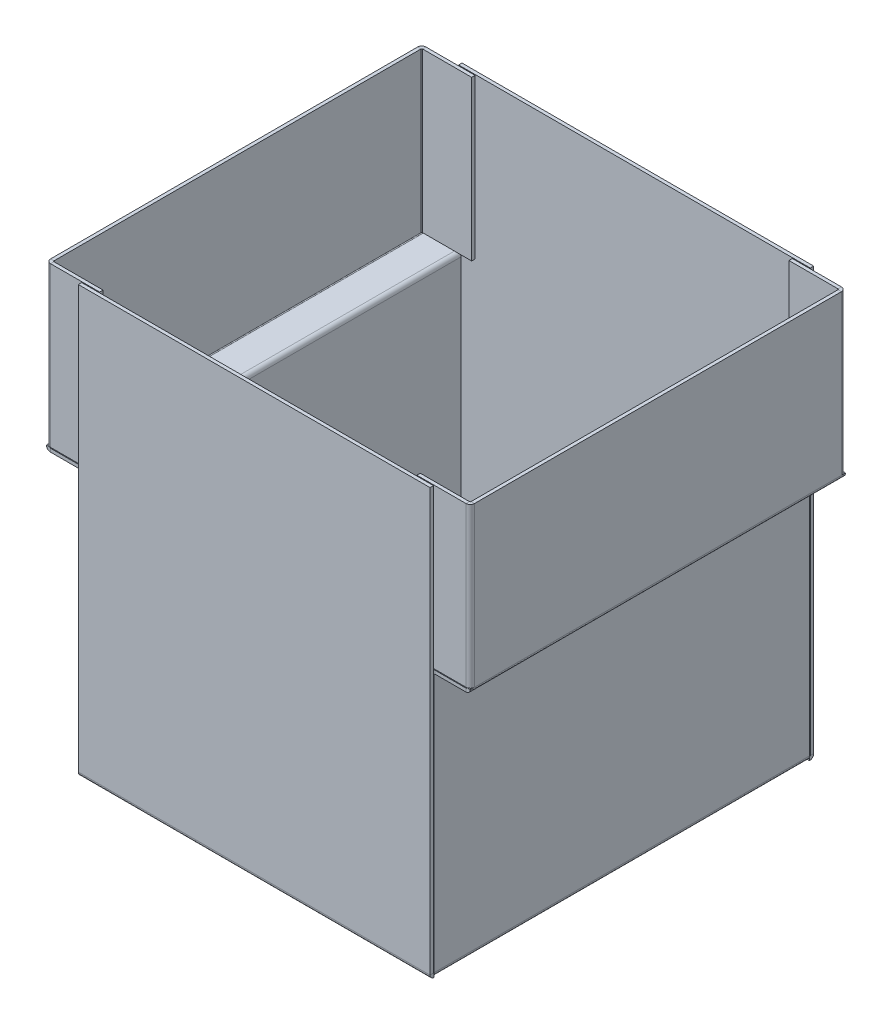
SolidWorks part; units mm, degrees
note: The reader was unsure of these and kept them because the rebuilt part matched: flange length of "Edge-Flange4", "Edge-Flange5", "Edge-Flange6", "Edge-Flange7", "Edge-Flange10", "Edge-Flange11", "Edge-Flange12", "Edge-Flange13", "Edge-Flange14".
material "6061 Alloy"
ref_plane "Front" through (0, 0, 0) normal (0, 0, 1) x (1, 0, 0)
ref_plane "Top" through (0, 0, 0) normal (0, 1, 0) x (1, 0, 0)
ref_plane "Right" through (0, 0, 0) normal (1, 0, 0) x (0, 0, -1)
sketch "Sketch6" plane through (0, 0, 0) normal (0, 1, 0) x (1, 0, 0)
  line L1 (-165, -180) -> (165, -180)
  line L2 (-165, -180) -> (-165, 180)
  line L3 (-165, 180) -> (165, 180)
  line L4 (165, -180) -> (165, 180)
  line L5 (-165, -180) -> (165, 180) construction
  line L6 (-165, 180) -> (165, -180) construction
  point P1 (0, 0)
  dimension "D1" = 360
  dimension "D2" = 330
base flange "Base-Flange2" sketch "Sketch6" thickness 3.175 reverse thickness direction no parameters "D1"=0.7366
edge flange "Edge-Flange4" sketch "Sketch34" flange angle 90 flange length 400 flange position material inside bend radius 0.7366 thickness 3.175 relief rectangular parameters "D6"=10
sketch "Sketch34" plane through (0, 0, 180) normal (0, 0, 1) x (1, 0, 0)
  line L0 (-165, 0) -> (165, 0) construction
  line L1 (-165, 0) -> (165, 0)
  line L2 (-165, 0) -> (-165, 396.825)
  line L3 (-165, 396.825) -> (165, 396.825)
  line L4 (165, 396.825) -> (165, 0)
bend "EdgeBend4" bend radius 0.7366 bend angle 90 parameters "D5"=1
edge flange "Edge-Flange5" sketch "Sketch37" flange angle 90 flange length 400 flange position material inside bend radius 0.7366 thickness 3.175 relief rectangular parameters "D6"=10
sketch "Sketch37" plane through (0, 0, -180) normal (0, 0, -1) x (-1, 0, 0)
  line L0 (-165, 0) -> (165, 0) construction
  line L1 (-165, 0) -> (165, 0)
  line L2 (-165, 0) -> (-165, 396.825)
  line L3 (-165, 396.825) -> (165, 396.825)
  line L4 (165, 396.825) -> (165, 0)
bend "EdgeBend5" bend radius 0.7366 bend angle 90 parameters "D5"=2
edge flange "Edge-Flange6" sketch "Sketch40" flange angle 90 flange length 250 flange position material inside bend radius 0.7366 thickness 3.175 relief none parameters "D6"=10
sketch "Sketch40" plane through (165, 0, 0) normal (1, 0, 0) x (0, 0, -1)
  line L0 (-176.0884, 0) -> (176.0884, 0) construction
  line L1 (-176.0884, 0) -> (176.0884, 0)
  line L2 (-176.0884, 0) -> (-176.0884, 246.825)
  line L3 (-176.0884, 246.825) -> (176.0884, 246.825)
  line L4 (176.0884, 246.825) -> (176.0884, 0)
bend "EdgeBend6" bend radius 0.7366 bend angle 90 parameters "D5"=3
edge flange "Edge-Flange7" sketch "Sketch43" flange angle 90 flange length 250 flange position material inside bend radius 0.7366 thickness 3.175 relief none parameters "D6"=10
sketch "Sketch43" plane through (-165, 0, 0) normal (-1, 0, 0) x (0, 0, 1)
  line L0 (-176.0884, 0) -> (176.0884, 0) construction
  line L1 (-176.0884, 0) -> (176.0884, 0)
  line L2 (-176.0884, 0) -> (-176.0884, 246.825)
  line L3 (-176.0884, 246.825) -> (176.0884, 246.825)
  line L4 (176.0884, 246.825) -> (176.0884, 0)
bend "EdgeBend7" bend radius 0.7366 bend angle 90 parameters "D5"=4
edge flange "Edge-Flange10" sketch "Sketch54" flange angle 90 flange length 37 flange position material inside bend radius 0.7366 thickness 3.175 relief rectangular parameters "D6"=10
sketch "Sketch54" plane through (-165, 246.825, 0) normal (0, 1, 0) x (0, 0, -1)
  line L0 (-176.0884, 0) -> (176.0884, 0) construction
  line L1 (-176.0884, 0) -> (176.0884, 0)
  line L2 (-176.0884, 0) -> (-176.0884, 33.825)
  line L3 (-176.0884, 33.825) -> (176.0884, 33.825)
  line L4 (176.0884, 33.825) -> (176.0884, 0)
bend "EdgeBend10" bend radius 0.7366 bend angle 90 parameters "D5"=5
edge flange "Edge-Flange11" sketch "Sketch57" flange angle 90 flange length 37 flange position material inside bend radius 0.7366 thickness 3.175 relief rectangular parameters "D6"=10
sketch "Sketch57" plane through (165, 246.825, 0) normal (0, 1, 0) x (0, 0, 1)
  line L0 (-176.0884, 0) -> (176.0884, 0) construction
  line L1 (-176.0884, 0) -> (176.0884, 0)
  line L2 (-176.0884, 0) -> (-176.0884, 33.825)
  line L3 (-176.0884, 33.825) -> (176.0884, 33.825)
  line L4 (176.0884, 33.825) -> (176.0884, 0)
bend "EdgeBend11" bend radius 0.7366 bend angle 90 parameters "D5"=6
edge flange "Edge-Flange12" sketch "Sketch60" flange angle 90 flange length 153.18 flange position material inside bend radius 0.7366 thickness 3.175 relief rectangular parameters "D6"=10
sketch "Sketch60" plane through (-198.825, 246.825, 0) normal (-1, 0, 0) x (0, 0, 1)
  line L2 (-176.0884, 0) -> (-176.0884, 150.005)
  line L3 (-176.0884, 150.005) -> (176.0884, 150.005)
  line L4 (176.0884, 150.005) -> (176.0884, 0)
  line L7 (-176.0884, 0) -> (176.0884, 0) construction
  line L8 (-176.0884, 0) -> (176.0884, 0)
bend "EdgeBend12" bend radius 0.7366 bend angle 90 parameters "D5"=7
edge flange "Edge-Flange13" sketch "Sketch63" flange angle 90 flange length 153.18 flange position material inside bend radius 0.7366 thickness 3.175 relief rectangular parameters "D6"=10
sketch "Sketch63" plane through (198.825, 246.825, 0) normal (1, 0, 0) x (0, 0, -1)
  line L0 (-176.0884, 0) -> (176.0884, 0) construction
  line L1 (-176.0884, 0) -> (176.0884, 0)
  line L2 (-176.0884, 0) -> (-176.0884, 150.005)
  line L3 (-176.0884, 150.005) -> (176.0884, 150.005)
  line L4 (176.0884, 150.005) -> (176.0884, 0)
bend "EdgeBend13" bend radius 0.7366 bend angle 90 parameters "D5"=8
edge flange "Edge-Flange14" sketch "Sketch68" flange profiles "Sketch68", "Sketch79", "Sketch81", "Sketch83" flange angle 90 flange length 50 bend radius 0.7366 thickness 3.175 relief none parameters "D6"=10, "D8"=1
sketch "Sketch68" plane through (-195.65, 0, 176.0884) normal (0, 0, 1) x (0, -1, 0)
  line L2 (-396.83, 0) -> (-396.83, 46.825)
  line L3 (-396.83, 46.825) -> (-247.5616, 46.825)
  line L4 (-247.5616, 46.825) -> (-247.5616, 0)
  line L15 (-247.5616, 0) -> (-396.83, 0) construction
  line L16 (-247.5616, 0) -> (-396.83, 0)
sketch "Sketch79" plane through (-195.65, 0, -176.0884) normal (0, 0, -1) x (0, 1, 0)
  line L0 (396.83, 0) -> (247.5616, 0) construction
  line L1 (396.83, 0) -> (247.5616, 0)
  line L2 (247.5616, 0) -> (247.5616, 46.825)
  line L3 (247.5616, 46.825) -> (396.83, 46.825)
  line L4 (396.83, 46.825) -> (396.83, 0)
sketch "Sketch81" plane through (195.65, 0, -176.0884) normal (0, 0, -1) x (0, -1, 0)
  line L0 (-247.5616, 0) -> (-396.83, 0) construction
  line L1 (-247.5616, 0) -> (-396.83, 0)
  line L2 (-396.83, 0) -> (-396.83, 46.825)
  line L3 (-396.83, 46.825) -> (-247.5616, 46.825)
  line L4 (-247.5616, 46.825) -> (-247.5616, 0)
sketch "Sketch83" plane through (195.65, 0, 176.0884) normal (0, 0, 1) x (0, 1, 0)
  line L0 (396.83, 0) -> (247.5616, 0) construction
  line L1 (396.83, 0) -> (247.5616, 0)
  line L2 (247.5616, 0) -> (247.5616, 46.825)
  line L3 (247.5616, 46.825) -> (396.83, 46.825)
  line L4 (396.83, 46.825) -> (396.83, 0)
bend "EdgeBend14" bend radius 0.7366 bend angle 90 parameters "D5"=9
bend "EdgeBend18" bend radius 0.7366 bend angle 90 parameters "D5"=11
bend "EdgeBend19" bend radius 0.7366 bend angle 90 parameters "D5"=12
bend "EdgeBend20" bend radius 0.7366 bend angle 90 parameters "D5"=13
sketch "Bend-Lines5" [suppressed] plane through (0, 0, 0) normal (0, 1, 0) x (1, 0, 0)
sketch "Bounding-Box5" [suppressed] plane through (0, 0, 0) normal (0, 1, 0) x (1, 0, 0)
sheet metal parameters "Sheet-Metal6" thickness 3.175 parameters "D1"=0.7366
flat pattern "Flat-Pattern6" [suppressed]
sketch "Bend-Lines6" plane through (0, 0, 0) normal (0, 1, 0) x (1, 0, 0)
sketch3d "Bounding-Box6" [suppressed]
  line L0 (-165.1, -177.8, 0) -> (-165.1, 177.8, 0) construction
  line L1 (165.1, -177.8, 0) -> (165.1, 177.8, 0) construction
  line L2 (-165.1, -177.8, 0) -> (165.1, -177.8, 0) construction
  line L3 (-165.1, 177.8, 0) -> (165.1, 177.8, 0) construction
sheet metal parameters "Sheet-Metal10" thickness 3.175 parameters "D1"=0.7366
flat pattern "Flat-Pattern6"
sketch "Bend-Lines6" plane through (0, 0, 0) normal (0, 1, 0) x (1, 0, 0)
  line L0 (-165.1, -175.7137) -> (165.1, -175.7137) construction
  line L1 (-165.1, -175.7137) -> (165.1, -175.7137) construction
sketch3d "Bounding-Box6" [suppressed]
  line L0 (-165.1, -478.4275, 0) -> (-165.1, 177.8, 0) construction
  line L1 (165.1, -478.4275, 0) -> (165.1, 177.8, 0) construction
  line L2 (-165.1, -478.4275, 0) -> (165.1, -478.4275, 0) construction
  line L3 (-165.1, 177.8, 0) -> (165.1, 177.8, 0) construction
bend of the flat pattern "Flatten-<EdgeBend4>1"
sheet metal parameters "Sheet-Metal11" thickness 3.175 parameters "D1"=0.7366
flat pattern "Flat-Pattern6"
sketch "Bend-Lines6" plane through (0, 0, 0) normal (0, 1, 0) x (1, 0, 0)
  line L0 (-165.1, -175.7137) -> (165.1, -175.7137) construction
  line L1 (-165.1, -175.7137) -> (165.1, -175.7137) construction
  line L2 (165.1, 175.7137) -> (-165.1, 175.7137) construction
  line L3 (165.1, 175.7137) -> (-165.1, 175.7137) construction
sketch3d "Bounding-Box6" [suppressed]
  line L0 (-165.1, -478.4275, 0) -> (-165.1, 478.4275, 0) construction
  line L1 (165.1, -478.4275, 0) -> (165.1, 478.4275, 0) construction
  line L2 (-165.1, -478.4275, 0) -> (165.1, -478.4275, 0) construction
  line L3 (-165.1, 478.4275, 0) -> (165.1, 478.4275, 0) construction
bend of the flat pattern "Flatten-<EdgeBend4>1"
bend of the flat pattern "Flatten-<EdgeBend5>1"
sheet metal parameters "Sheet-Metal12" thickness 3.175 parameters "D1"=0.7366
flat pattern "Flat-Pattern6"
sketch "Bend-Lines6" plane through (0, 0, 0) normal (0, 1, 0) x (1, 0, 0)
  line L0 (-165.1, -175.7137) -> (165.1, -175.7137) construction
  line L1 (-165.1, -175.7137) -> (165.1, -175.7137) construction
  line L2 (165.1, 175.7137) -> (-165.1, 175.7137) construction
  line L3 (165.1, 175.7137) -> (-165.1, 175.7137) construction
  line L4 (163.0137, -173.8884) -> (163.0137, 173.8884) construction
  line L5 (163.0137, -173.8884) -> (163.0137, 173.8884) construction
sketch3d "Bounding-Box6" [suppressed]
  line L0 (-165.1, -478.4275, 0) -> (-165.1, 478.4275, 0) construction
  line L1 (465.7275, -478.4275, 0) -> (465.7275, 478.4275, 0) construction
  line L2 (-165.1, -478.4275, 0) -> (465.7275, -478.4275, 0) construction
  line L3 (-165.1, 478.4275, 0) -> (465.7275, 478.4275, 0) construction
bend of the flat pattern "Flatten-<EdgeBend4>1"
bend of the flat pattern "Flatten-<EdgeBend5>1"
bend of the flat pattern "Flatten-<EdgeBend6>1"
sheet metal parameters "Sheet-Metal13" thickness 3.175 parameters "D1"=0.7366
flat pattern "Flat-Pattern6"
sketch "Bend-Lines6" plane through (0, 0, 0) normal (0, 1, 0) x (1, 0, 0)
  line L0 (-152.4, -175.7137) -> (152.4, -175.7137) construction
  line L1 (-152.4, -175.7137) -> (152.4, -175.7137) construction
  line L2 (152.4, 175.7137) -> (-152.4, 175.7137) construction
  line L3 (152.4, 175.7137) -> (-152.4, 175.7137) construction
  line L4 (150.3137, -173.8884) -> (150.3137, 173.8884) construction
  line L5 (150.3137, -173.8884) -> (150.3137, 173.8884) construction
  line L6 (-150.3137, 173.8884) -> (-150.3137, -173.8884) construction
  line L7 (-150.3137, 173.8884) -> (-150.3137, -173.8884) construction
sketch3d "Bounding-Box6" [suppressed]
  line L0 (630.7875, -6.1835, 0) -> (1.9697, 630.8148, 0) construction
  line L1 (-1.9694, -630.8144, 0) -> (-630.7872, 6.1838, 0) construction
  line L2 (630.7875, -6.1835, 0) -> (-1.9694, -630.8144, 0) construction
  line L3 (1.9697, 630.8148, 0) -> (-630.7872, 6.1838, 0) construction
bend of the flat pattern "Flatten-<EdgeBend4>1"
bend of the flat pattern "Flatten-<EdgeBend5>1"
bend of the flat pattern "Flatten-<EdgeBend6>1"
bend of the flat pattern "Flatten-<EdgeBend7>1"
sheet metal parameters "Sheet-Metal16" thickness 3.175 parameters "D1"=0.7366
flat pattern "Flat-Pattern6"
sketch "Bend-Lines6" plane through (0, 0, 0) normal (0, 1, 0) x (1, 0, 0)
  line L0 (-152.4, -175.7137) -> (152.4, -175.7137) construction
  line L1 (-152.4, -175.7137) -> (152.4, -175.7137) construction
  line L2 (152.4, 175.7137) -> (-152.4, 175.7137) construction
  line L3 (152.4, 175.7137) -> (-152.4, 175.7137) construction
  line L4 (150.3137, -173.8884) -> (150.3137, 173.8884) construction
  line L5 (150.3137, -173.8884) -> (150.3137, 173.8884) construction
  line L6 (-150.3137, 173.8884) -> (-150.3137, -173.8884) construction
  line L7 (-150.3137, 173.8884) -> (-150.3137, -173.8884) construction
  line L8 (-450.9412, 173.8884) -> (-450.9412, -173.8884) construction
  line L9 (-450.9412, 173.8884) -> (-450.9412, -173.8884) construction
sketch3d "Bounding-Box6" [suppressed]
  line L0 (-648.1288, -2.2478, 0) -> (-12.721, 641.4276, 0) construction
  line L1 (-4.6203, -637.4909, 0) -> (630.7875, 6.1845, 0) construction
  line L2 (-648.1288, -2.2478, 0) -> (-4.6203, -637.4909, 0) construction
  line L3 (-12.721, 641.4276, 0) -> (630.7875, 6.1845, 0) construction
bend of the flat pattern "Flatten-<EdgeBend4>1"
bend of the flat pattern "Flatten-<EdgeBend5>1"
bend of the flat pattern "Flatten-<EdgeBend6>1"
bend of the flat pattern "Flatten-<EdgeBend7>1"
bend of the flat pattern "Flatten-<EdgeBend10>1"
sheet metal parameters "Sheet-Metal17" thickness 3.175 parameters "D1"=0.7366
flat pattern "Flat-Pattern6"
sketch "Bend-Lines6" plane through (0, 0, 0) normal (0, 1, 0) x (1, 0, 0)
  line L0 (-152.4, -175.7137) -> (152.4, -175.7137) construction
  line L1 (-152.4, -175.7137) -> (152.4, -175.7137) construction
  line L2 (152.4, 175.7137) -> (-152.4, 175.7137) construction
  line L3 (152.4, 175.7137) -> (-152.4, 175.7137) construction
  line L4 (150.3137, -173.8884) -> (150.3137, 173.8884) construction
  line L5 (150.3137, -173.8884) -> (150.3137, 173.8884) construction
  line L6 (-150.3137, 173.8884) -> (-150.3137, -173.8884) construction
  line L7 (-150.3137, 173.8884) -> (-150.3137, -173.8884) construction
  line L8 (-450.9412, 173.8884) -> (-450.9412, -173.8884) construction
  line L9 (-450.9412, 173.8884) -> (-450.9412, -173.8884) construction
  line L10 (450.9412, -173.8884) -> (450.9412, 173.8884) construction
  line L11 (450.9412, -173.8884) -> (450.9412, 173.8884) construction
sketch3d "Bounding-Box6" [suppressed]
  line L0 (647.8778, 9.6065, 0) -> (-26.2004, 647.4191, 0) construction
  line L1 (26.2004, -647.4191, 0) -> (-647.8778, -9.6065, 0) construction
  line L2 (647.8778, 9.6065, 0) -> (26.2004, -647.4191, 0) construction
  line L3 (-26.2004, 647.4191, 0) -> (-647.8778, -9.6065, 0) construction
bend of the flat pattern "Flatten-<EdgeBend4>1"
bend of the flat pattern "Flatten-<EdgeBend5>1"
bend of the flat pattern "Flatten-<EdgeBend6>1"
bend of the flat pattern "Flatten-<EdgeBend7>1"
bend of the flat pattern "Flatten-<EdgeBend10>1"
bend of the flat pattern "Flatten-<EdgeBend11>1"
sheet metal parameters "Sheet-Metal18" thickness 3.175 parameters "D1"=0.7366
flat pattern "Flat-Pattern6"
sketch "Bend-Lines6" plane through (0, 0, 0) normal (0, 1, 0) x (1, 0, 0)
  line L0 (-152.4, -175.7137) -> (152.4, -175.7137) construction
  line L1 (-152.4, -175.7137) -> (152.4, -175.7137) construction
  line L2 (152.4, 175.7137) -> (-152.4, 175.7137) construction
  line L3 (152.4, 175.7137) -> (-152.4, 175.7137) construction
  line L4 (150.3137, -173.8884) -> (150.3137, 173.8884) construction
  line L5 (150.3137, -173.8884) -> (150.3137, 173.8884) construction
  line L6 (-150.3137, 173.8884) -> (-150.3137, -173.8884) construction
  line L7 (-150.3137, 173.8884) -> (-150.3137, -173.8884) construction
  line L8 (-450.9412, 173.8884) -> (-450.9412, -173.8884) construction
  line L9 (-450.9412, 173.8884) -> (-450.9412, -173.8884) construction
  line L10 (450.9412, -173.8884) -> (450.9412, 173.8884) construction
  line L11 (450.9412, -173.8884) -> (450.9412, 173.8884) construction
  line L12 (-472.1687, 173.8884) -> (-472.1687, -173.8884) construction
  line L13 (-472.1687, 173.8884) -> (-472.1687, -173.8884) construction
sketch3d "Bounding-Box6" [suppressed]
  line L0 (647.8778, 9.6065, 0) -> (-50.8021, 670.6972, 0) construction
  line L1 (4.1746, -670.6972, 0) -> (-694.5053, -9.6065, 0) construction
  line L2 (647.8778, 9.6065, 0) -> (4.1746, -670.6972, 0) construction
  line L3 (-50.8021, 670.6972, 0) -> (-694.5053, -9.6065, 0) construction
bend of the flat pattern "Flatten-<EdgeBend4>1"
bend of the flat pattern "Flatten-<EdgeBend5>1"
bend of the flat pattern "Flatten-<EdgeBend6>1"
bend of the flat pattern "Flatten-<EdgeBend7>1"
bend of the flat pattern "Flatten-<EdgeBend10>1"
bend of the flat pattern "Flatten-<EdgeBend11>1"
bend of the flat pattern "Flatten-<EdgeBend12>1"
sheet metal parameters "Sheet-Metal19" thickness 3.175 parameters "D1"=0.7366
flat pattern "Flat-Pattern6"
sketch "Bend-Lines6" plane through (0, 0, 0) normal (0, 1, 0) x (1, 0, 0)
  line L0 (-152.4, -175.7137) -> (152.4, -175.7137) construction
  line L1 (-152.4, -175.7137) -> (152.4, -175.7137) construction
  line L2 (152.4, 175.7137) -> (-152.4, 175.7137) construction
  line L3 (152.4, 175.7137) -> (-152.4, 175.7137) construction
  line L4 (150.3137, -173.8884) -> (150.3137, 173.8884) construction
  line L5 (150.3137, -173.8884) -> (150.3137, 173.8884) construction
  line L6 (-150.3137, 173.8884) -> (-150.3137, -173.8884) construction
  line L7 (-150.3137, 173.8884) -> (-150.3137, -173.8884) construction
  line L8 (-450.9412, 173.8884) -> (-450.9412, -173.8884) construction
  line L9 (-450.9412, 173.8884) -> (-450.9412, -173.8884) construction
  line L10 (450.9412, -173.8884) -> (450.9412, 173.8884) construction
  line L11 (450.9412, -173.8884) -> (450.9412, 173.8884) construction
  line L12 (-472.1687, 173.8884) -> (-472.1687, -173.8884) construction
  line L13 (-472.1687, 173.8884) -> (-472.1687, -173.8884) construction
  line L14 (472.1687, -173.8884) -> (472.1687, 173.8884) construction
  line L15 (472.1687, -173.8884) -> (472.1687, 173.8884) construction
sketch3d "Bounding-Box6" [suppressed]
  line L0 (694.6562, 6.313, 0) -> (-18.9105, 694.4275, 0) construction
  line L1 (18.9105, -694.4275, 0) -> (-694.6562, -6.313, 0) construction
  line L2 (694.6562, 6.313, 0) -> (18.9105, -694.4275, 0) construction
  line L3 (-18.9105, 694.4275, 0) -> (-694.6562, -6.313, 0) construction
bend of the flat pattern "Flatten-<EdgeBend4>1"
bend of the flat pattern "Flatten-<EdgeBend5>1"
bend of the flat pattern "Flatten-<EdgeBend6>1"
bend of the flat pattern "Flatten-<EdgeBend7>1"
bend of the flat pattern "Flatten-<EdgeBend10>1"
bend of the flat pattern "Flatten-<EdgeBend11>1"
bend of the flat pattern "Flatten-<EdgeBend12>1"
bend of the flat pattern "Flatten-<EdgeBend13>1"
sheet metal parameters "Sheet-Metal20" thickness 3.175 parameters "D1"=0.7366
flat pattern "Flat-Pattern6"
sketch "Bend-Lines6" plane through (0, 0, 0) normal (0, 1, 0) x (1, 0, 0)
  line L0 (-165, -177.9137) -> (165, -177.9137) construction
  line L1 (-165, -177.9137) -> (165, -177.9137) construction
  line L2 (165, 177.9137) -> (-165, 177.9137) construction
  line L3 (165, 177.9137) -> (-165, 177.9137) construction
  line L4 (162.9137, -176.0884) -> (162.9137, 176.0884) construction
  line L5 (162.9137, -176.0884) -> (162.9137, 176.0884) construction
  line L6 (-162.9137, 176.0884) -> (-162.9137, -176.0884) construction
  line L7 (-162.9137, 176.0884) -> (-162.9137, -176.0884) construction
  line L8 (-408.7412, 176.0884) -> (-408.7412, -176.0884) construction
  line L9 (-408.7412, 176.0884) -> (-408.7412, -176.0884) construction
  line L10 (408.7412, -176.0884) -> (408.7412, 176.0884) construction
  line L11 (408.7412, -176.0884) -> (408.7412, 176.0884) construction
  line L12 (-441.5687, 176.0884) -> (-441.5687, -176.0884) construction
  line L13 (-441.5687, 176.0884) -> (-441.5687, -176.0884) construction
  line L14 (441.5687, -176.0884) -> (441.5687, 176.0884) construction
  line L15 (441.5687, -176.0884) -> (441.5687, 176.0884) construction
  line L16 (-592.6625, -174.0021) -> (-443.3941, -174.0021) construction
  line L17 (-592.6625, -174.0021) -> (-443.3941, -174.0021) construction
  line L18 (443.3941, -174.0021) -> (592.6625, -174.0021) construction
  line L19 (592.6625, 174.0021) -> (443.3941, 174.0021) construction
  line L20 (-443.3941, 174.0021) -> (-592.6625, 174.0021) construction
  line L21 (443.3941, -174.0021) -> (592.6625, -174.0021) construction
  line L22 (592.6625, 174.0021) -> (443.3941, 174.0021) construction
  line L23 (-443.3941, 174.0021) -> (-592.6625, 174.0021) construction
sketch3d "Bounding-Box6" [suppressed]
  line L0 (810.6613, 41.5112, 0) -> (-110.8624, 804.1172, 0) construction
  line L1 (110.8624, -804.1172, 0) -> (-810.6613, -41.5112, 0) construction
  line L2 (810.6613, 41.5112, 0) -> (110.8624, -804.1172, 0) construction
  line L3 (-110.8624, 804.1172, 0) -> (-810.6613, -41.5112, 0) construction
bend of the flat pattern "Flatten-<EdgeBend4>1"
bend of the flat pattern "Flatten-<EdgeBend5>1"
bend of the flat pattern "Flatten-<EdgeBend6>1"
bend of the flat pattern "Flatten-<EdgeBend7>1"
bend of the flat pattern "Flatten-<EdgeBend10>1"
bend of the flat pattern "Flatten-<EdgeBend11>1"
bend of the flat pattern "Flatten-<EdgeBend12>1"
bend of the flat pattern "Flatten-<EdgeBend13>1"
bend of the flat pattern "Flatten-<EdgeBend14>1"
bend of the flat pattern "Flatten-<EdgeBend18>1"
bend of the flat pattern "Flatten-<EdgeBend19>1"
bend of the flat pattern "Flatten-<EdgeBend20>1"
